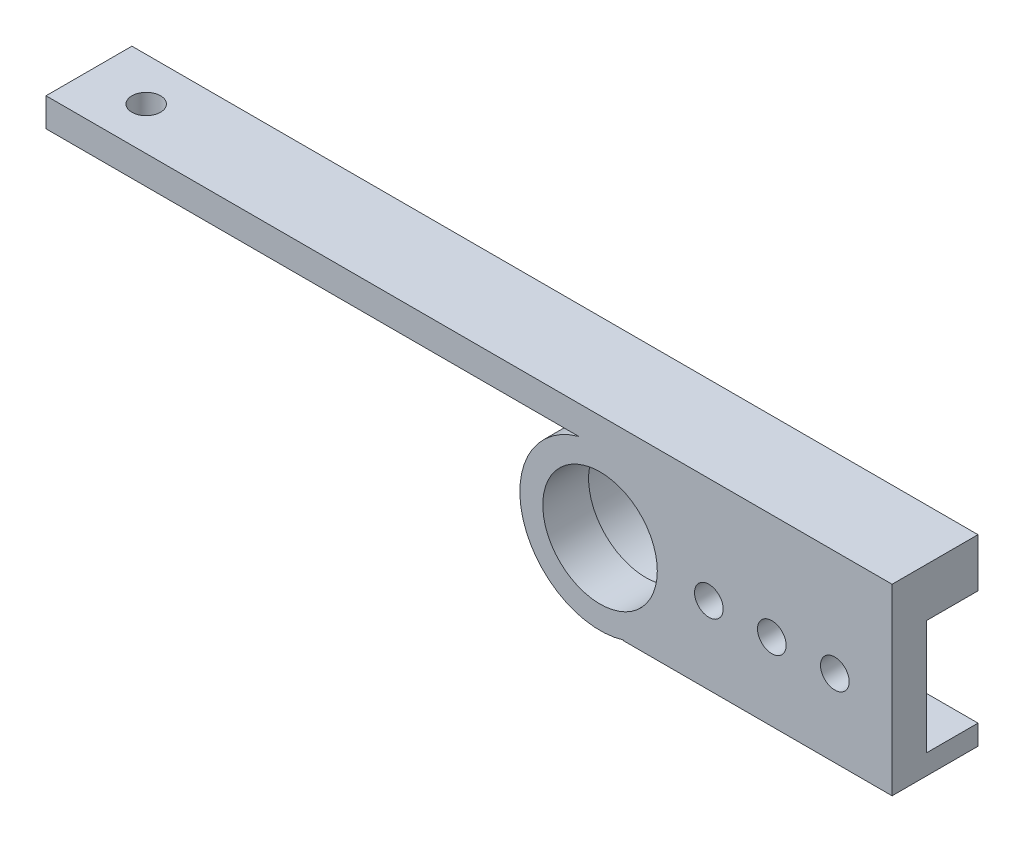
SolidWorks part; units mm, degrees
ref_plane "前视基准面" through (0, 0, 0) normal (0, 0, 1) x (1, 0, 0)
ref_plane "上视基准面" through (0, 0, 0) normal (0, 1, 0) x (1, 0, 0)
ref_plane "右视基准面" through (0, 0, 0) normal (1, 0, 0) x (0, 0, -1)
sketch "草图1" plane through (0, 0, 0) normal (0, 0, 1) x (1, 0, 0)
  line L1 (20, -10) -> (-20, -10)
  line L2 (20, -10) -> (20, 10)
  line L3 (20, 10) -> (-20, 10)
  line L4 (-20, -10) -> (-20, 10)
  line L5 (20, -10) -> (-20, 10) construction
  line L6 (20, 10) -> (-20, -10) construction
  point P0 (0, 0)
  dimension "D1" = 40
  dimension "D2" = 20
extrude "凸台-拉伸1" add sketch "草图1" along normal blind 6
sketch "草图2" plane through (0, 0, 6) normal (0, 0, 1) x (1, 0, 0)
  line L0 (20, -10) -> (20, 10) construction
  circle A0 centre (10, 0) radius 2.5
  circle A1 centre (-1, 0) radius 2.5
  circle A2 centre (-12, 0) radius 2.5
  dimension "D1" = 10
  dimension "D2" = 5
  dimension "D3" = 3
extrude "切除-拉伸1" cut sketch "草图2" against normal through all
sketch "草图3" plane through (0, 0, 6) normal (0, 0, 1) x (1, 0, 0)
  line L0 (20, 13.5) -> (20, 10)
  line L1 (20, -13.5) -> (-26.894, -13.5)
  line L3 (20, 13.5) -> (-26.894, 13.5)
  line L4 (-20, 10) -> (-20, -10)
  line L5 (-20, -10) -> (20, -10)
  line L6 (20, -10) -> (20, 10)
  line L7 (20, 10) -> (-20, 10)
  line L8 (-20, 10) -> (-20, -10)
  line L9 (-20, -10) -> (20, -10)
  line L10 (20, -10) -> (20, 10)
  line L11 (20, 10) -> (-20, 10)
  line L12 (-26.894, -13.5) -> (-26.894, 13.5)
  line L13 (20, -10.0394) -> (-26.894, 13.5) construction
  line L14 (20, 10.0394) -> (-26.894, -13.5) construction
  line L15 (20, -10) -> (20, -13.5)
  circle A0 centre (-31, 0) radius 11
  circle A1 centre (-31, 0) radius 14
  point P2 (0, 0)
  line M10 (-20, 10) -> (-20, -10)
  line M11 (-20, -10) -> (20, -10)
  line M13 (20, 10) -> (-20, 10)
  dimension "D3" = 22
  dimension "D4" = 28
  dimension "D2" = 3.5
  dimension "D1" = 0
extrude "凸台-拉伸2" add sketch "草图3" against normal blind 15 contours L3 A1 L1 L12 A0 | A1 L1 L15 M11 M10 | L1 A1 L8 A0 L12 | L8 A1 L3 L12 A0 | L8 A1 | A1 L0 L3 M10 M13 region at (-1.9449, 11.7771, 6) region at (-1.9449, -11.7771, 6) region at (-23.0173, 9.0328, 6) region at (-27.2274, 11.7946, 6) region at (-18.7882, 0, 6) region at (-23.0173, -9.0328, 6)
sketch "草图5" plane through (0, 0, 6) normal (0, 0, 1) x (1, 0, 0)
  circle A0 centre (-31, 0) radius 10
  circle A1 centre (-31, 0) radius 11 construction
  circle A2 centre (-31, 0) radius 11
  dimension "D1" = 20
extrude "凸台-拉伸3" add sketch "草图5" against normal blind 8
sketch "草图6" plane through (0, 0, 6) normal (0, 0, 1) x (1, 0, 0)
  circle A0 centre (-31, 0) radius 8.5
  circle A1 centre (-31, 0) radius 10 construction
  circle A2 centre (-31, 0) radius 10
  dimension "D1" = 17
sketch "草图7" plane through (0, 13.5, 0) normal (0, 1, 0) x (1, 0, 0)
  circle A0 centre (-16.8213, 3.0525) radius 3.3366
sketch "草图8" plane through (20, 0, 0) normal (1, 0, 0) x (0, 0, -1)
  line L1 (-6, 13.5) -> (9, 13.5)
  line L2 (-6, 13.5) -> (-6, 18.5)
  line L3 (-6, 18.5) -> (9, 18.5)
  line L4 (9, 13.5) -> (9, 18.5)
  dimension "D1" = 5
extrude "凸台-拉伸4" add sketch "草图8" against normal blind 200
sketch "草图9" plane through (0, 0, 6) normal (0, 0, 1) x (1, 0, 0)
  line L1 (-29.5663, 15.6648) -> (-25.1627, 15.6648)
  line L2 (-29.5663, 15.6648) -> (-29.5663, 11.9284)
  line L3 (-29.5663, 11.9284) -> (-25.1627, 11.9284)
  line L4 (-25.1627, 15.6648) -> (-25.1627, 11.9284)
extrude "凸台-拉伸5" add sketch "草图9" against normal through all
sketch "草图11" plane through (0, 18.5, 0) normal (0, 1, 0) x (1, 0, 0)
  line L0 (-127.7451, -6) -> (-127.7451, 9)
  line L1 (-180, -6) -> (20, -6) construction
  line L2 (-127.7451, 245.09) -> (-127.7451, -124.91) construction
  line L3 (-180, 9) -> (20, 9) construction
sketch "草图13" plane through (0, 18.5, 0) normal (0, 1, 0) x (1, 0, 0)
  line L1 (-127.7451, -6) -> (-183.1111, -6)
  line L2 (-127.7451, -6) -> (-127.7451, 12.5245)
  line L3 (-127.7451, 12.5245) -> (-183.1111, 12.5245)
  line L4 (-183.1111, -6) -> (-183.1111, 12.5245)
extrude "切除-拉伸2" cut sketch "草图13" against normal through all
sketch "草图14" plane through (0, 18.5, 0) normal (0, 1, 0) x (1, 0, 0)
  line L0 (-127.7451, 1.5) -> (-117.7451, 1.5) construction
  line L1 (-127.7451, -6) -> (-127.7451, 9) construction
  circle A0 centre (-117.7451, 1.5) radius 2.5
  dimension "D1" = 5
  dimension "D2" = 10
extrude "切除-拉伸3" cut sketch "草图14" against normal through all
